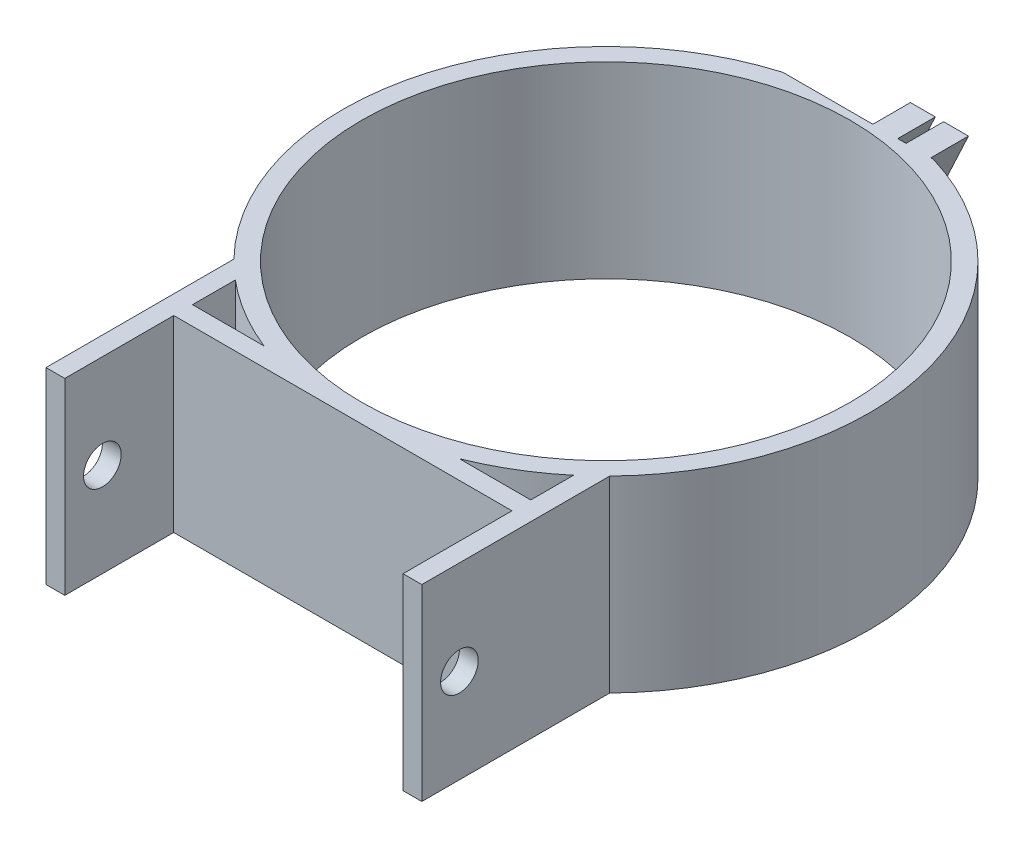
SolidWorks part; units mm, degrees
material "ABS"
ref_plane "Front Plane" through (0, 0, 0) normal (0, 0, 1) x (1, 0, 0)
ref_plane "Top Plane" through (0, 0, 0) normal (0, 1, 0) x (1, 0, 0)
ref_plane "Right Plane" through (0, 0, 0) normal (1, 0, 0) x (0, 0, -1)
sketch "Sketch1" plane through (0, 0, 0) normal (0, 1, 0) x (1, 0, 0)
  line L0 (0, 0) -> (0, 57.3018) construction
  line L1 (0, 0) -> (0, -45.4787) construction
  line L2 (-22.5, -35) -> (22.5, -35)
  line L3 (-25, -35) -> (-25, -24.4949)
  line L4 (25, -35) -> (25, -24.4949)
  line L5 (-22.5, -26.8095) -> (-22.5, -32.5)
  line L6 (-22.5, -32.5) -> (-12.9904, -32.5)
  line L7 (22.5, -32.5) -> (22.5, -26.8095)
  line L8 (12.9904, -32.5) -> (22.5, -32.5)
  line L9 (-22.5, -35) -> (-22.5, -49.4949)
  line L10 (-10, 38.541) -> (10, 38.541)
  line L11 (-10, 38.541) -> (-10, 33.541)
  line L12 (-22.5, -49.4949) -> (-25, -49.4949)
  line L13 (10, 38.541) -> (10, 33.541)
  line L14 (-10, 38.541) -> (10, 33.541) construction
  line L15 (-10, 33.541) -> (10, 38.541) construction
  line L16 (-25, -49.4949) -> (-25, -35)
  line L17 (22.5, -35) -> (22.5, -49.4949)
  line L18 (22.5, -49.4949) -> (25, -49.4949)
  line L19 (25, -49.4949) -> (25, -35)
  circle A0 centre (0, 0) radius 32.5
  arc A1 (-22.5, -26.8095) -> (-12.9904, -32.5) centre (0, 0) ccw
  arc A2 (25, -24.4949) -> (10, 33.541) centre (0, 0) ccw
  arc A3 (12.9904, -32.5) -> (22.5, -26.8095) centre (0, 0) ccw
  arc A4 (-10, 33.541) -> (-25, -24.4949) centre (0, 0) ccw
  point P3 (0, 36.041)
  dimension "D1" = 65
  dimension "D2" = 70
  dimension "D3" = 35
  dimension "D4" = 50
  dimension "D5" = 2.5
  dimension "D6" = 2.5
  dimension "D7" = 2.5
  dimension "D8" = 20
  dimension "D9" = 5
  dimension "D10" = 25
extrude "Boss-Extrude1" add sketch "Sketch1" along normal blind 25
sketch "Sketch2" plane through (0, 0, -38.541) normal (0, 0, -1) x (-1, 0, 0)
  line L0 (-5.8288, 25) -> (5.8288, 0) construction
  line L1 (-10, 25) -> (10, 25) construction
  line L2 (-10, 0) -> (10, 0) construction
  line L3 (-6.3805, 25) -> (5.2772, 0)
  line L4 (-5.2772, 25) -> (6.3805, 0)
  line L5 (0, 0) -> (0, 25) construction
  line L6 (-6.3805, 25) -> (-5.2772, 25)
  line L7 (6.3805, 0) -> (5.2772, 0)
  line L8 (-1.967, 25) -> (10, 25)
  line L9 (10, 25) -> (10, 0)
  line L10 (10, 0) -> (9.6907, 0)
  line L11 (9.6907, 0) -> (-1.967, 25)
  line L12 (-9.6907, 25) -> (-10, 25)
  line L13 (-10, 25) -> (-10, -0.0298)
  line L14 (-10, 25) -> (-10, 0) construction
  line L15 (-10, 25) -> (-10, 0) construction
  line L16 (-10, -0.0298) -> (1.967, 0)
  line L17 (1.967, 0) -> (-9.6907, 25)
  point P12 (0, 12.5)
  point P13 (0, 25)
  dimension "D1" = 65
  dimension "D2" = 0.5
  dimension "D3" = 0.5
  dimension "D4" = 3
  dimension "D5" = 3
extrude "Cut-Extrude1" cut sketch "Sketch2" against normal blind 5
ref_axis "Axis1" through (0, 26.25, 0) along (0, -1, 0)
sketch "Sketch3" plane through (25, 0, 0) normal (1, 0, 0) x (0, 0, -1)
  line L0 (-49.4949, 25) -> (-49.4949, 0) construction
  line L1 (-49.4949, 25) -> (-24.4949, 25) construction
  circle A0 centre (-44.4949, 12.5) radius 2.5
  point P4 (0, 0)
  point P6 (-42.5035, 25.5161)
  dimension "D1" = 5
  dimension "D2" = 5
  dimension "D3" = 12.5
extrude "Cut-Extrude2" cut sketch "Sketch3" against normal through all both and the other way through all
